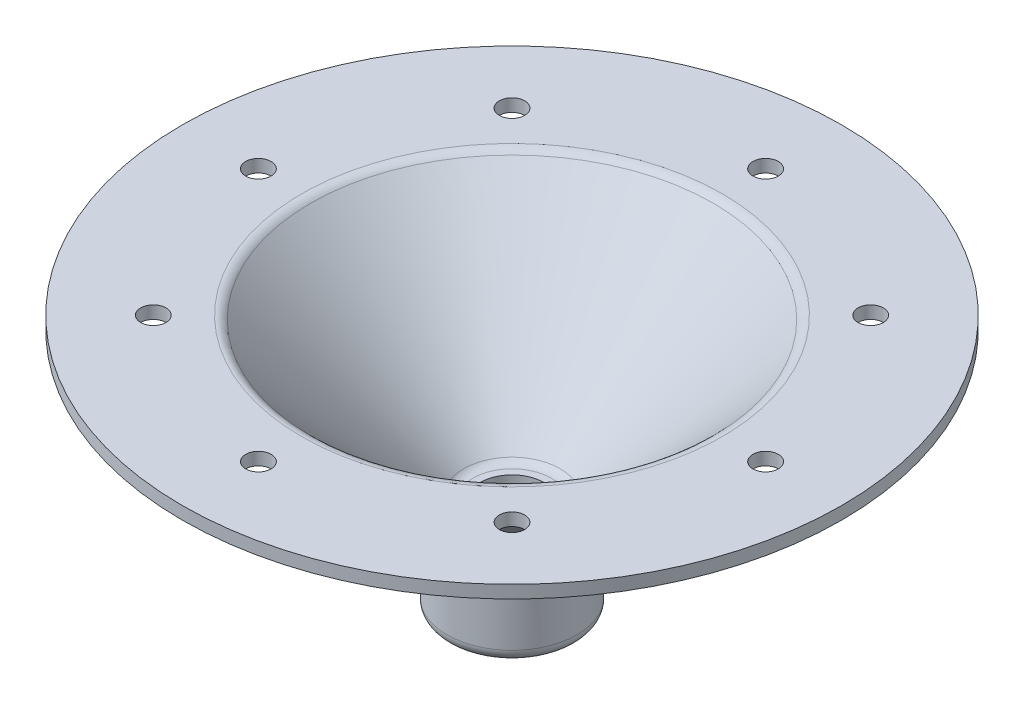
SolidWorks part; units mm, degrees
ref_plane "Front Plane" through (0, 0, 0) normal (0, 0, 1) x (1, 0, 0)
ref_plane "Top Plane" through (0, 0, 0) normal (0, 1, 0) x (1, 0, 0)
ref_plane "Right Plane" through (0, 0, 0) normal (1, 0, 0) x (0, 0, -1)
sketch "Sketch1" plane through (0, 0, 0) normal (0, 0, 1) x (1, 0, 0)
  line L0 (0, 0) -> (0, 44.3889) construction
  line L1 (-4.953, -9.525) -> (-4.953, 0)
  line L2 (-4.953, 0) -> (-3.9688, 0)
  line L3 (-3.9688, 0) -> (-3.9688, 2.54)
  line L4 (-3.9688, 2.54) -> (-5.5563, 2.54)
  line L5 (-5.5563, 2.54) -> (-25.6724, 22.6561)
  line L6 (-25.6724, 22.6561) -> (-41.275, 22.6561)
  line L7 (-41.275, 22.6561) -> (-41.275, 21.0686)
  line L8 (-41.275, 21.0686) -> (-28.575, 21.0686)
  line L9 (-28.575, 21.0686) -> (-8.128, 0.6216)
  line L10 (-8.128, 0.6216) -> (-8.128, -9.525)
  line L11 (-8.128, -9.525) -> (-4.953, -9.525)
  dimension "D1" = 57.15
  dimension "D2" = 7.9375
  dimension "D3" = 9.906
  dimension "D4" = 9.525
  dimension "D5" = 2.54
  dimension "D6" = 3.175
  dimension "D7" = 45
  dimension "D8" = 1.5875
  dimension "D9" = 3.175
  dimension "D10" = 1.5875
  dimension "D11" = 82.55
revolve "Revolve1" add sketch "Sketch1" angle 360 about L0
sketch "Sketch2" plane through (0, 22.6561, 0) normal (0, 1, 0) x (1, 0, 0)
  circle A0 centre (-31.75, 0) radius 1.5875
  dimension "D1" = 3.175
  dimension "D2" = 31.75
ref_axis "Axis1" through (0, 24.1064, 0) along (0, -1, 0)
extrude "Cut-Extrude1" cut sketch "Sketch2" against normal through all
sketch "Sketch3" [suppressed] plane through (0, 21.0686, 0) normal (0, -1, 0) x (1, 0, 0)
  circle A0 centre (-29.3687, 0) radius 1.5875
  circle A1 centre (-29.3687, 0) radius 5.5562
  circle A2 centre (0, 0) radius 34.925 construction
  circle A3 centre (-29.3687, 0) radius 1.5875 construction
extrude "Boss-Extrude4" [suppressed] add sketch "Sketch3" along normal offset from surface (7.9375 mm away) 9.525 up to face at (-31.75, 22.6561, 1.5875)
pattern_circular "CirPattern1" count 8 over 360 about axis through (0, 24.1064, 0) along (0, -1, 0) of "Cut-Extrude1"
fillet "Fillet1" radius 1.5875 6 edges at (0, 21.0686, -28.575) (0, -9.525, -4.953) (0, -9.525, -8.128) (0, 0.6216, -8.128) (0, 2.54, -5.5563) (0, 22.6561, -25.6724)
